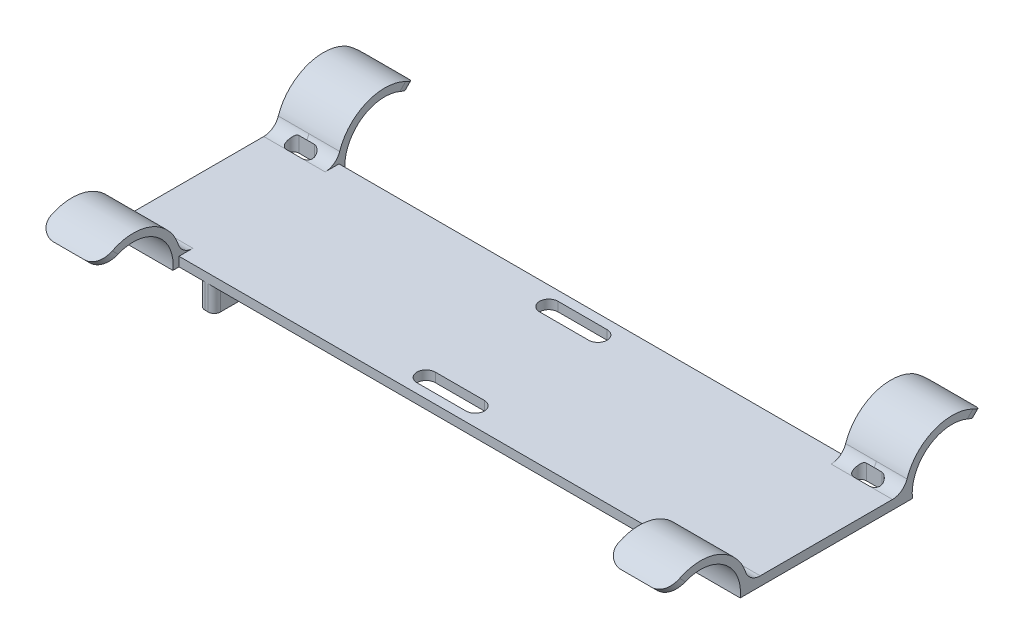
SolidWorks part; units mm, degrees
note: The reader was unsure of these and kept them because the rebuilt part matched: shared geometry of "Sketch5<3>".
ref_plane "Front Plane" through (0, 0, 0) normal (0, 0, 1) x (1, 0, 0)
ref_plane "Top Plane" through (0, 0, 0) normal (0, 1, 0) x (1, 0, 0)
ref_plane "Right Plane" through (0, 0, 0) normal (1, 0, 0) x (0, 0, -1)
sketch "Sketch2" plane through (0, 0, 0) normal (1, 0, 0) x (0, 0, -1)
  line L0 (-41, 0) -> (41, 0) construction
  line L1 (-41, 0) -> (-51.9602, 10.9602)
  line L2 (-28.0868, 1.5) -> (28.0868, 1.5)
  line L3 (-32.3877, 1.5) -> (-32.3877, -1.5) construction
  line L4 (-28.0868, -1.5) -> (28.0868, -1.5)
  line L6 (41, 0) -> (51.9602, 10.9602)
  circle A0 centre (41, 0) radius 13
  circle A1 centre (-41, 0) radius 13
  circle A2 centre (-41, 0) radius 15.5
  circle A3 centre (41, 0) radius 15.5
  point P6 (0, 0)
  point P14 (-32.3877, 0)
  dimension "D2" = 26
  dimension "D7" = 31
  dimension "D1" = 82
  dimension "D4" = 3
  dimension "D5" = 45
  dimension "D6" = 45
extrude "Boss-Extrude2" add sketch "Sketch2" along normal mid plane 205 contours L2 A2 L1 A1 | L4 A2 L2 A1 | A3 L2 A2 L4 | L2 A3 L4 A0 | L6 A3 L2 A0
sketch "Sketch5" plane through (0, 1.5, 0) normal (0, 1, 0) x (1, 0, 0)
  line L0 (102.5, 51.9602) -> (-102.5, 51.9602) construction
  line L1 (-82.5, 51.9602) -> (82.5, 51.9602)
  line L2 (-82.5, 51.9602) -> (-82.5, -51.9602)
  line L3 (-82.5, -51.9602) -> (82.5, -51.9602)
  line L4 (82.5, 51.9602) -> (82.5, -51.9602)
  line L6 (-92.5, 51.9602) -> (-92.5, -51.9602) construction
  line L7 (102.5, -51.9602) -> (-102.5, -51.9602) construction
  line L8 (92.5, 51.9602) -> (92.5, -51.9602) construction
  line L9 (-95, 23.5728) -> (-90, 23.5728) construction
  line L10 (-95, 25.5728) -> (-90, 25.5728)
  line L11 (-95, 21.5728) -> (-90, 21.5728)
  line L12 (102.5, 25.5728) -> (-102.5, 25.5728) construction
  line L13 (-82.5, 0) -> (82.5, 0) construction
  line L14 (0, 51.9602) -> (0, -51.9602) construction
  line L15 (-95, -23.5728) -> (-90, -23.5728) construction
  line L16 (-95, -25.5728) -> (-90, -25.5728)
  line L17 (-95, -21.5728) -> (-90, -21.5728)
  line L18 (95, 23.5728) -> (90, 23.5728) construction
  line L19 (95, 25.5728) -> (90, 25.5728)
  line L20 (95, 21.5728) -> (90, 21.5728)
  line L21 (95, -23.5728) -> (90, -23.5728) construction
  line L22 (95, -25.5728) -> (90, -25.5728)
  line L23 (95, -21.5728) -> (90, -21.5728)
  line L24 (-8, 20) -> (8, 20) construction
  line L25 (-8, 23) -> (8, 23)
  line L26 (-8, 17) -> (8, 17)
  line L27 (-8, -20) -> (8, -20) construction
  line L28 (-8, -23) -> (8, -23)
  line L29 (-8, -17) -> (8, -17)
  arc A0 (-95, 25.5728) -> (-95, 21.5728) centre (-95, 23.5728) ccw
  arc A1 (-90, 21.5728) -> (-90, 25.5728) centre (-90, 23.5728) ccw
  arc A2 (-95, -25.5728) -> (-95, -21.5728) centre (-95, -23.5728) cw
  arc A3 (-90, -21.5728) -> (-90, -25.5728) centre (-90, -23.5728) cw
  arc A4 (95, 25.5728) -> (95, 21.5728) centre (95, 23.5728) cw
  arc A5 (90, 21.5728) -> (90, 25.5728) centre (90, 23.5728) cw
  arc A6 (95, -25.5728) -> (95, -21.5728) centre (95, -23.5728) ccw
  arc A7 (90, -21.5728) -> (90, -25.5728) centre (90, -23.5728) ccw
  arc A8 (-8, 23) -> (-8, 17) centre (-8, 20) ccw
  arc A9 (8, 17) -> (8, 23) centre (8, 20) ccw
  arc A10 (-8, -23) -> (-8, -17) centre (-8, -20) cw
  arc A11 (8, -17) -> (8, -23) centre (8, -20) cw
  point P4 (-82.5, 0)
  point P6 (0, 51.9602)
  point P17 (-92.5, 23.5728)
  point P30 (-92.5, -23.5728)
  point P37 (92.5, 23.5728)
  point P44 (92.5, -23.5728)
  point P51 (0, 20)
  point P56 (0, 0)
  point P60 (0, -20)
  line M14 (-102.5, -25.5728) -> (102.5, -25.5728)
  line M16 (102.5, 25.5728) -> (-102.5, 25.5728)
  dimension "D4" = 2
  dimension "D1" = 165
  dimension "D2" = 10
  dimension "D3" = 10
  dimension "D5" = 5
  dimension "D6" = 16
  dimension "D7" = 40
  dimension "D8" = 3
extrude "Cut-Extrude1" cut sketch "Sketch5" along normal through all contours L4 L2 M16 M14 | L4 L1 L2 M16 | L4 L2 L3 M14
extrude "Cut-Extrude2" cut sketch "Sketch5<3>" against normal up to next contours L26 A9 A8 M16 | A11 L29 A10 M14 | A3 L16 A2 L17 | A1 L10 A0 L11 | A5 L19 A4 L20 | A7 L22 A6 L23
sketch "Sketch5<3>" plane through (0, 1.5, 0) normal (0, 1, 0) x (1, 0, 0) same geometry as "Sketch5"
fillet "Fillet1" radius 5 8 edges at (-86.25, 1.5, 25.5728) (86.25, 1.5, 25.5728) (86.25, 1.5, -25.5728) (-98.75, 1.5, -25.5728) (98.75, 1.5, 25.5728) (98.75, 1.5, -25.5728) (-98.75, 1.5, 25.5728) (-86.25, 1.5, -25.5728)
fillet "Fillet2" radius 5 8 edges at (-82.5, 10.0763, -51.0763) (-102.5, 10.0763, -51.0763) (82.5, 10.0763, -51.0763) (102.5, 10.0763, -51.0763) (82.5, 10.0763, 51.0763) (102.5, 10.0763, 51.0763) (-102.5, 10.0763, 51.0763) (-82.5, 10.0763, 51.0763)
sketch "Sketch6" plane through (0, 1.5, 0) normal (0, 1, 0) x (1, 0, 0)
  line L0 (-82.5, 28.0868) -> (82.5, 28.0868) construction
  line L1 (-82.5, 26.0868) -> (82.5, 26.0868)
  line L2 (-82.5, 26.0868) -> (-82.5, -26.0868)
  line L3 (-82.5, -26.0868) -> (82.5, -26.0868)
  line L4 (82.5, 26.0868) -> (82.5, -26.0868)
  point P4 (82.5, 0)
  point P6 (0, 26.0868)
  line M9 (82.5, -28.0868) -> (82.5, -21.5578)
  line M15 (82.5, 21.5578) -> (82.5, 28.0868)
  line M16 (82.5, 28.0868) -> (-82.5, 28.0868)
  line M17 (-82.5, 28.0868) -> (-82.5, 21.5578)
  line M23 (-82.5, -21.5578) -> (-82.5, -28.0868)
  line M24 (-82.5, -28.0868) -> (82.5, -28.0868)
  dimension "D1" = 2
extrude "Cut-Extrude3" cut sketch "Sketch6" against normal up to next contours L1 M17 M15 M16 | L3 M23 M24 M9
sketch "Sketch7" plane through (0, -1.5, 0) normal (0, -1, 0) x (-1, 0, 0)
  line L0 (-71, 26.0868) -> (-71, -26.0868)
  line L1 (-82.5, 26.0868) -> (82.5, 26.0868)
  line L2 (-82.5, 26.0868) -> (-82.5, -26.0868)
  line L3 (-82.5, -26.0868) -> (82.5, -26.0868)
  line L4 (82.5, 26.0868) -> (82.5, -26.0868)
  line L5 (71, 26.0868) -> (71, -26.0868)
  line L6 (-71, 0) -> (71, 0) construction
  line L7 (-76, 26.0868) -> (-76, -26.0868)
  line L8 (76, 26.0868) -> (76, -26.0868)
  point P12 (0, 0)
  line M11 (82.5, 26.0868) -> (-82.5, 26.0868)
  dimension "D1" = 142
  dimension "D2" = 5
  dimension "D3" = 5
extrude "Boss-Extrude3" add sketch "Sketch7" along normal blind 8 contours L7 L3 L0 M11 | L8 L1 L5 L3
fillet "Fillet3" radius 2 8 edges at (-71, -5.5, 26.0868) (-76, -5.5, 26.0868) (71, -5.5, 26.0868) (76, -5.5, 26.0868) (71, -5.5, -26.0868) (76, -5.5, -26.0868) (-76, -5.5, -26.0868) (-71, -5.5, -26.0868)
